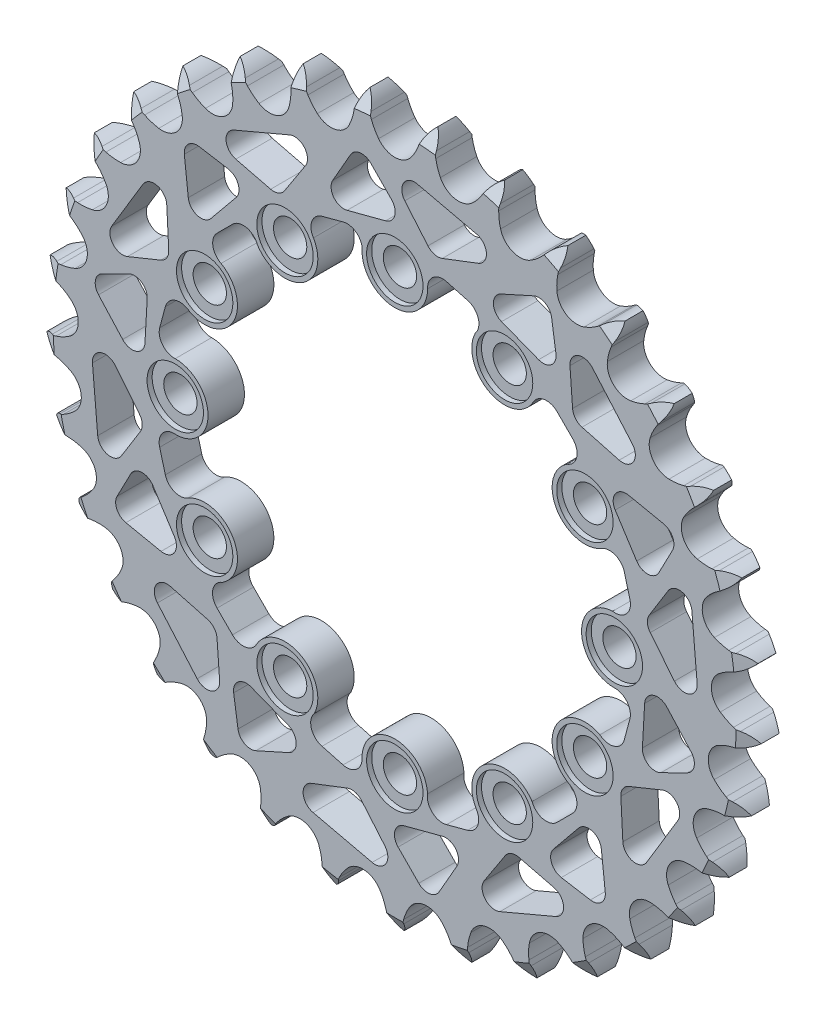
SolidWorks part; units mm, degrees
material "7075-T6 (SN)"
ref_plane "Front Plane" through (0, 0, 0) normal (0, 0, 1) x (1, 0, 0)
ref_plane "Top Plane" through (0, 0, 0) normal (0, 1, 0) x (1, 0, 0)
ref_plane "Right Plane" through (0, 0, 0) normal (1, 0, 0) x (0, 0, -1)
sketch "Work Sketch" plane through (0, 0, 0) normal (0, 0, 1) x (1, 0, 0)
  line L0 (0, 0) -> (0, 160.4542) construction
  line L1 (-112.0919, 66.8027) -> (87.2579, 66.8027) construction
  line L2 (5.0834, 120.8822) -> (5.0834, 112.9699) construction
  line L3 (-12.8497, 70.6081) -> (16.7256, 70.6081) construction
  line L4 (5.0834, 70.6081) -> (-6.0658, 62.2619) construction
  line L5 (5.0834, 70.6081) -> (-4.6352, 66.9715) construction
  line L6 (-4.6352, 66.9715) -> (-6.998, 73.2861)
  line L7 (-11.5114, 65.7464) -> (-7.1525, 65.7464) construction
  line L8 (-11.0622, 124.7602) -> (-11.0622, 110.2345) construction
  line L9 (0, 0) -> (-4.0639, 42.5596) construction
  circle A0 centre (0, 0) radius 66.8027
  circle A1 centre (0, 66.8027) radius 4.0088
  arc A2 (-4.6352, 66.9715) -> (-3.2092, 64.4003) centre (5.0609, 70.6677) ccw
  circle A3 centre (-11.0622, 65.7464) radius 6.4488
  point P23 (-3.2092, 64.4003)
  dimension "D1" = 133.6054
  dimension "D8" = 10.3767
  dimension "D2" = 8.0177
  dimension "D3" = 5.0834
  dimension "D4" = 3.8054
  dimension "D5" = 36.818
  dimension "D6" = 16.303
  dimension "D7" = 10.3767
  dimension "D9" = 1.0563
  dimension "D10" = 11.0622
  dimension "D11" = 5.455
sketch "Teeth Sketch" plane through (0, 0, 0) normal (0, 0, 1) x (1, 0, 0)
  line L0 (5.0224, 68.0064) -> (4.6352, 66.9715)
  line L1 (-8.8439, 92.6176) -> (-5.6513, 59.1829) construction
  line L2 (0, 0) -> (-12.8498, 132.1321) construction
  line L3 (7.9387, 67.7279) -> (8.123, 66.6385)
  line L4 (19011.2087, -199094.3845) -> (-19015.2726, 199136.9441) construction
  line L5 (0, 146.3285) -> (0, 56.9858) construction
  line L6 (17.8019, 65.8269) -> (17.2258, 64.8841)
  line L7 (0, -200000) -> (0, 200160.4542) construction
  line L8 (20.6128, 65.0016) -> (20.5877, 63.897)
  line L9 (-4.6352, 66.9715) -> (-6.998, 73.2861) construction
  line L10 (43.2949, 52.6844) -> (42.861, 51.6682)
  line L11 (-5.0224, 68.0064) -> (-4.6352, 66.9715)
  line L12 (29.938, 61.2683) -> (29.1939, 60.4515)
  line L13 (32.5419, 59.9259) -> (32.3082, 58.846)
  line L14 (40.9921, 54.4953) -> (40.1069, 53.8341)
  line L15 (50.5647, 45.7527) -> (49.5703, 45.271)
  line L16 (52.4831, 43.5387) -> (51.8648, 42.623)
  line L17 (58.3096, 35.3565) -> (57.2421, 35.0716)
  line L18 (59.7744, 32.8194) -> (58.9939, 32.0373)
  line L19 (63.9472, 23.6824) -> (62.845, 23.6047)
  line L20 (64.9053, 20.9139) -> (63.9909, 20.2936)
  line L21 (67.2735, 11.1523) -> (66.1765, 11.2846)
  line L22 (67.6904, 8.2526) -> (66.6751, 7.8165)
  line L23 (68.1683, -1.7808) -> (67.1162, -1.4433)
  line L24 (68.0289, -4.7071) -> (66.9495, -4.9431)
  line L25 (66.5994, -14.6496) -> (65.6302, -14.119)
  line L26 (65.9088, -17.4966) -> (64.8042, -17.524)
  line L27 (62.6234, -26.9889) -> (61.7722, -26.2845)
  line L28 (61.4065, -29.6537) -> (60.3166, -29.4716)
  line L29 (56.3841, -38.3527) -> (55.6815, -37.4999)
  line L30 (54.6848, -40.739) -> (53.6491, -40.354)
  line L31 (48.1068, -48.3304) -> (47.5783, -47.3601)
  line L32 (45.9866, -50.352) -> (45.0425, -49.7779)
  line L33 (38.0909, -56.5613) -> (37.7556, -55.5085)
  line L34 (35.6264, -58.1451) -> (34.808, -57.4027)
  line L35 (26.6983, -62.7479) -> (26.5682, -61.6506)
  line L36 (23.9786, -63.8367) -> (23.3155, -62.9529)
  line L37 (14.3407, -66.6666) -> (14.4207, -65.5646)
  line L38 (11.4641, -67.221) -> (10.9802, -66.2277)
  line L39 (1.4648, -68.1759) -> (1.7519, -67.1089)
  line L40 (-1.4648, -68.1759) -> (-1.7519, -67.1089)
  line L41 (-11.4641, -67.221) -> (-10.9802, -66.2277)
  line L42 (-14.3407, -66.6666) -> (-14.4207, -65.5646)
  line L43 (-23.9786, -63.8367) -> (-23.3155, -62.9529)
  line L44 (-26.6983, -62.7479) -> (-26.5682, -61.6506)
  line L45 (-35.6264, -58.1451) -> (-34.808, -57.4027)
  line L46 (-38.0909, -56.5613) -> (-37.7556, -55.5085)
  line L47 (-45.9866, -50.352) -> (-45.0425, -49.7779)
  line L48 (-48.1068, -48.3304) -> (-47.5783, -47.3601)
  line L49 (-54.6848, -40.739) -> (-53.6491, -40.354)
  line L50 (-56.3841, -38.3527) -> (-55.6815, -37.4999)
  line L51 (-61.4065, -29.6537) -> (-60.3166, -29.4716)
  line L52 (-62.6234, -26.9889) -> (-61.7722, -26.2845)
  line L53 (-65.9088, -17.4966) -> (-64.8042, -17.524)
  line L54 (-66.5994, -14.6496) -> (-65.6302, -14.119)
  line L55 (-68.0289, -4.7071) -> (-66.9495, -4.9431)
  line L56 (-68.1683, -1.7808) -> (-67.1162, -1.4433)
  line L57 (-67.6904, 8.2526) -> (-66.6751, 7.8165)
  line L58 (-67.2735, 11.1523) -> (-66.1765, 11.2846)
  line L59 (-64.9053, 20.9139) -> (-63.9909, 20.2936)
  line L60 (-63.9472, 23.6824) -> (-62.845, 23.6047)
  line L61 (-59.7744, 32.8194) -> (-58.9939, 32.0373)
  line L62 (-58.3096, 35.3565) -> (-57.2421, 35.0716)
  line L63 (-52.4831, 43.5387) -> (-51.8648, 42.623)
  line L64 (-50.5647, 45.7527) -> (-49.5703, 45.271)
  line L65 (-43.2949, 52.6844) -> (-42.861, 51.6682)
  line L66 (-40.9921, 54.4953) -> (-40.1069, 53.8341)
  line L67 (-32.5419, 59.9259) -> (-32.3082, 58.846)
  line L68 (-29.938, 61.2683) -> (-29.1939, 60.4515)
  line L69 (-20.6128, 65.0016) -> (-20.5877, 63.897)
  line L70 (-17.8019, 65.8269) -> (-17.2258, 64.8841)
  line L71 (-7.9387, 67.7279) -> (-8.123, 66.6385)
  arc A0 (-6.7346, 70.5274) -> (-5.0224, 68.0064) centre (-11.0622, 65.7464) cw
  circle A1 centre (-11.0622, 65.7464) radius 6.4488 construction
  arc A2 (-3.2092, 64.4003) -> (-4.6352, 66.9715) centre (5.0609, 70.6677) cw
  arc A3 (-4.6352, 66.9715) -> (-3.2092, 64.4003) centre (5.0609, 70.6677) ccw construction
  circle A4 centre (0, 66.8027) radius 4.0088 construction
  arc A5 (-3.2092, 64.4003) -> (3.2092, 64.4003) centre (0, 66.8027) ccw
  arc A6 (3.2092, 64.4003) -> (4.6352, 66.9715) centre (-5.0609, 70.6677) ccw
  arc A7 (6.7346, 70.5274) -> (5.0224, 68.0064) centre (11.0622, 65.7464) ccw
  arc A8 (6.7346, 70.5274) -> (7.9387, 67.7279) centre (1.5803, 66.6518) cw
  arc A9 (9.0366, 63.8438) -> (8.123, 66.6385) centre (18.3434, 68.4328) cw
  arc A10 (9.0366, 63.8438) -> (15.3391, 62.6291) centre (12.6425, 65.5955) ccw
  arc A11 (15.3391, 62.6291) -> (17.2258, 64.8841) centre (8.4044, 70.3484) ccw
  arc A12 (19.9603, 67.9784) -> (17.8019, 65.8269) centre (23.3049, 62.4647) ccw
  arc A13 (19.9603, 67.9784) -> (20.6128, 65.0016) centre (14.1657, 65.1482) cw
  arc A14 (20.9558, 60.9799) -> (20.5877, 63.897) centre (30.9629, 63.7246) cw
  arc A15 (20.9558, 60.9799) -> (26.9145, 58.5944) centre (24.8281, 62.0175) ccw
  arc A16 (26.9145, 58.5944) -> (29.1939, 60.4515) centre (21.5661, 67.4865) ccw
  arc A17 (32.4645, 62.9724) -> (29.938, 61.2683) centre (34.7052, 56.9254) ccw
  arc A18 (32.4645, 62.9724) -> (32.5419, 59.9259) centre (26.2391, 61.29) cw
  arc A19 (32.1176, 55.912) -> (32.3082, 58.846) centre (42.4634, 56.7133) cw
  arc A20 (32.1176, 55.912) -> (37.5172, 52.4419) centre (36.1163, 56.198) ccw
  arc A21 (37.5172, 52.4419) -> (40.1069, 53.8341) centre (33.9483, 62.1856) ccw
  arc A22 (43.7955, 55.6905) -> (40.9921, 54.4953) centre (44.8513, 49.3287) ccw
  arc A23 (43.7955, 55.6905) -> (43.2949, 52.6844) centre (37.3641, 55.2167) cw
  arc A24 (42.1187, 48.8233) -> (42.861, 51.6682) centre (52.429, 47.6521) cw
  arc A25 (42.1187, 48.8233) -> (46.7639, 44.3941) centre (46.0991, 48.3474) ccw
  arc A26 (46.7639, 44.3941) -> (49.5703, 45.271) centre (45.1035, 54.637) ccw
  arc A27 (53.5435, 46.3957) -> (50.5647, 45.7527) centre (53.3763, 39.9491) ccw
  arc A28 (53.5435, 46.3957) -> (52.4831, 43.5387) centre (47.1387, 47.1476) cw
  arc A29 (50.5974, 39.97) -> (51.8648, 42.623) centre (60.4998, 36.8687) cw
  arc A30 (50.5974, 39.97) -> (54.3205, 34.7417) centre (54.4159, 38.7494) ccw
  arc A31 (54.3205, 34.7417) -> (57.2421, 35.0716) centre (54.6285, 45.1138) ccw
  arc A32 (61.3564, 35.4241) -> (58.3096, 35.3565) centre (59.9721, 29.1257) ccw
  arc A33 (61.3564, 35.4241) -> (59.7744, 32.8194) centre (55.2096, 37.3746) cw
  arc A34 (57.2474, 29.6721) -> (58.9939, 32.0373) centre (66.384, 24.7528) cw
  arc A35 (57.2474, 29.6721) -> (59.9137, 23.8336) centre (60.7659, 27.7508) ccw
  arc A36 (59.9137, 23.8336) -> (62.845, 23.6047) centre (62.1792, 33.96) ccw
  arc A37 (66.9516, 23.1722) -> (63.9472, 23.6824) centre (64.4004, 17.2495) ccw
  arc A38 (66.9516, 23.1722) -> (64.9053, 20.9139) centre (61.2851, 26.2507) cw
  arc A39 (61.8283, 18.3017) -> (63.9909, 20.2936) centre (69.8688, 11.7422) cw
  arc A40 (61.8283, 18.3017) -> (63.3416, 12.0642) centre (64.9196, 15.7493) ccw
  arc A41 (63.3416, 12.0642) -> (66.1765, 11.2846) centre (67.4825, 21.5788) ccw
  arc A42 (70.1271, 10.0828) -> (67.2735, 11.1523) centre (66.5011, 4.7499) ccw
  arc A43 (70.1271, 10.0828) -> (67.6904, 8.2526) centre (65.1456, 14.178) cw
  arc A44 (64.1746, 6.2699) -> (66.6751, 7.8165) centre (70.8284, -1.6927) cw
  arc A45 (64.1746, 6.2699) -> (64.48, -0.1413) centre (66.727, 3.1786) ccw
  arc A46 (64.48, -0.1413) -> (67.1162, -1.4433) centre (70.3468, 8.4177) ccw
  arc A47 (70.768, -3.3711) -> (68.1683, -1.7808) centre (66.1983, -7.9213) ccw
  arc A48 (70.768, -3.3711) -> (68.0289, -4.7071) centre (66.6515, 1.5929) cw
  arc A49 (64.2015, -5.9885) -> (66.9495, -4.9431) centre (69.2281, -15.0665) cw
  arc A50 (64.2015, -5.9885) -> (63.2881, -12.3417) centre (66.1227, -9.507) ccw
  arc A51 (63.2881, -12.3417) -> (65.6302, -14.119) centre (70.6686, -5.0476) ccw
  arc A52 (68.8511, -16.7031) -> (66.5994, -14.6496) centre (63.5029, -20.3063) ccw
  arc A53 (68.8511, -16.7031) -> (65.9088, -17.4966) centre (65.7485, -11.0498) cw
  arc A54 (61.908, -18.0305) -> (64.8042, -17.524) centre (65.1257, -27.8957) cw
  arc A55 (61.908, -18.0305) -> (59.8087, -24.096) centre (63.1286, -21.849) ccw
  arc A56 (59.8087, -24.096) -> (61.7722, -26.2845) centre (68.4363, -18.3305) ccw
  arc A57 (64.4458, -29.4314) -> (62.6234, -26.9889) centre (58.5123, -31.9573) ccw
  arc A58 (64.4458, -29.4314) -> (61.4065, -29.6537) centre (62.4691, -23.2931) cw
  arc A59 (57.3769, -29.4209) -> (60.3166, -29.4716) centre (58.6695, -39.7167) cw
  arc A60 (57.3769, -29.4209) -> (54.1677, -34.9794) centre (57.8528, -33.4013) ccw
  arc A61 (54.1677, -34.9794) -> (55.6815, -37.4999) centre (63.7305, -30.9509) ccw
  arc A62 (57.7113, -41.096) -> (56.3841, -38.3527) centre (51.4069, -42.4533) ccw
  arc A63 (57.7113, -41.096) -> (54.6848, -40.739) centre (56.932, -34.6945) cw
  arc A64 (50.7721, -39.7478) -> (53.6491, -40.354) centre (50.0928, -50.1023) cw
  arc A65 (50.7721, -39.7478) -> (46.5689, -44.5986) centre (50.4861, -43.7465) ccw
  arc A66 (46.5689, -44.5986) -> (47.5783, -47.3601) centre (56.7213, -42.4527) ccw
  arc A67 (48.8909, -51.2753) -> (48.1068, -48.3304) centre (42.4436, -51.415) ccw
  arc A68 (48.8909, -51.2753) -> (45.9866, -50.352) centre (49.3372, -44.842) cw
  arc A69 (42.3322, -48.6382) -> (45.0425, -49.7779) centre (39.7057, -58.677) cw
  arc A70 (42.3322, -48.6382) -> (37.287, -52.6059) centre (41.2947, -52.5105) ccw
  arc A71 (37.287, -52.6059) -> (37.7556, -55.5085) centre (47.662, -52.4201) ccw
  arc A72 (38.3034, -59.6013) -> (38.0909, -56.5613) centre (31.9463, -58.5183) ccw
  arc A73 (38.3034, -59.6013) -> (35.6264, -58.1451) centre (39.9592, -53.3687) cw
  arc A74 (32.3624, -55.7707) -> (34.808, -57.4027) centre (27.8834, -65.131) cw
  arc A75 (32.3624, -55.7707) -> (26.6574, -58.7118) centre (30.6108, -59.3766) ccw
  arc A76 (26.6574, -58.7118) -> (26.5682, -61.6506) centre (36.8801, -60.4929) ccw
  arc A77 (26.3316, -65.7732) -> (26.6983, -62.7479) centre (20.2943, -63.5067) ccw
  arc A78 (26.3316, -65.7732) -> (23.9786, -63.8367) centre (29.137, -59.9666) cw
  arc A79 (21.2229, -60.8875) -> (23.3155, -62.9529) centre (15.0534, -69.2309) cw
  arc A80 (21.2229, -60.8875) -> (15.0644, -62.6958) centre (18.8205, -64.0967) ccw
  arc A81 (15.0644, -62.6958) -> (14.4207, -65.5646) centre (24.7653, -66.3793) ccw
  arc A82 (13.4081, -69.5679) -> (14.3407, -66.6666) centre (7.9088, -66.1998) ccw
  arc A83 (13.4081, -69.5679) -> (11.4641, -67.221) centre (17.2617, -64.3972) cw
  arc A84 (9.3163, -63.8036) -> (10.9802, -66.2277) centre (1.6794, -70.8287) cw
  arc A85 (9.3163, -63.8036) -> (2.9269, -64.4137) centre (6.35, -66.5002) ccw
  arc A86 (2.9269, -64.4137) -> (1.7519, -67.1089) centre (11.7554, -69.8666) ccw
  arc A87 (0, -70.8482) -> (1.4648, -68.1759) centre (-4.7625, -66.5002) ccw
  arc A88 (0, -70.8482) -> (-1.4648, -68.1759) centre (4.7625, -66.5002) cw
  arc A89 (-2.9269, -64.4137) -> (-1.7519, -67.1089) centre (-11.7554, -69.8666) cw
  arc A90 (-2.9269, -64.4137) -> (-9.3163, -63.8036) centre (-6.35, -66.5002) ccw
  arc A91 (-9.3163, -63.8036) -> (-10.9802, -66.2277) centre (-1.6794, -70.8287) ccw
  arc A92 (-13.4081, -69.5679) -> (-11.4641, -67.221) centre (-17.2617, -64.3972) ccw
  arc A93 (-13.4081, -69.5679) -> (-14.3407, -66.6666) centre (-7.9088, -66.1998) cw
  arc A94 (-15.0644, -62.6958) -> (-14.4207, -65.5646) centre (-24.7653, -66.3793) cw
  arc A95 (-15.0644, -62.6958) -> (-21.2229, -60.8875) centre (-18.8205, -64.0967) ccw
  arc A96 (-21.2229, -60.8875) -> (-23.3155, -62.9529) centre (-15.0534, -69.2309) ccw
  arc A97 (-26.3316, -65.7732) -> (-23.9786, -63.8367) centre (-29.137, -59.9666) ccw
  arc A98 (-26.3316, -65.7732) -> (-26.6983, -62.7479) centre (-20.2943, -63.5067) cw
  arc A99 (-26.6574, -58.7118) -> (-26.5682, -61.6506) centre (-36.8801, -60.4929) cw
  arc A100 (-26.6574, -58.7118) -> (-32.3624, -55.7707) centre (-30.6108, -59.3766) ccw
  arc A101 (-32.3624, -55.7707) -> (-34.808, -57.4027) centre (-27.8834, -65.131) ccw
  arc A102 (-38.3034, -59.6013) -> (-35.6264, -58.1451) centre (-39.9592, -53.3687) ccw
  arc A103 (-38.3034, -59.6013) -> (-38.0909, -56.5613) centre (-31.9463, -58.5183) cw
  arc A104 (-37.287, -52.6059) -> (-37.7556, -55.5085) centre (-47.662, -52.4201) cw
  arc A105 (-37.287, -52.6059) -> (-42.3322, -48.6382) centre (-41.2947, -52.5105) ccw
  arc A106 (-42.3322, -48.6382) -> (-45.0425, -49.7779) centre (-39.7057, -58.677) ccw
  arc A107 (-48.8909, -51.2753) -> (-45.9866, -50.352) centre (-49.3372, -44.842) ccw
  arc A108 (-48.8909, -51.2753) -> (-48.1068, -48.3304) centre (-42.4436, -51.415) cw
  arc A109 (-46.5689, -44.5986) -> (-47.5783, -47.3601) centre (-56.7213, -42.4527) cw
  arc A110 (-46.5689, -44.5986) -> (-50.7721, -39.7478) centre (-50.4861, -43.7465) ccw
  arc A111 (-50.7721, -39.7478) -> (-53.6491, -40.354) centre (-50.0928, -50.1023) ccw
  arc A112 (-57.7113, -41.096) -> (-54.6848, -40.739) centre (-56.932, -34.6945) ccw
  arc A113 (-57.7113, -41.096) -> (-56.3841, -38.3527) centre (-51.4069, -42.4533) cw
  arc A114 (-54.1677, -34.9794) -> (-55.6815, -37.4999) centre (-63.7305, -30.9509) cw
  arc A115 (-54.1677, -34.9794) -> (-57.3769, -29.4209) centre (-57.8528, -33.4013) ccw
  arc A116 (-57.3769, -29.4209) -> (-60.3166, -29.4716) centre (-58.6695, -39.7167) ccw
  arc A117 (-64.4458, -29.4314) -> (-61.4065, -29.6537) centre (-62.4691, -23.2931) ccw
  arc A118 (-64.4458, -29.4314) -> (-62.6234, -26.9889) centre (-58.5123, -31.9573) cw
  arc A119 (-59.8087, -24.096) -> (-61.7722, -26.2845) centre (-68.4363, -18.3305) cw
  arc A120 (-59.8087, -24.096) -> (-61.908, -18.0305) centre (-63.1286, -21.849) ccw
  arc A121 (-61.908, -18.0305) -> (-64.8042, -17.524) centre (-65.1257, -27.8957) ccw
  arc A122 (-68.8511, -16.7031) -> (-65.9088, -17.4966) centre (-65.7485, -11.0498) ccw
  arc A123 (-68.8511, -16.7031) -> (-66.5994, -14.6496) centre (-63.5029, -20.3063) cw
  arc A124 (-63.2881, -12.3417) -> (-65.6302, -14.119) centre (-70.6686, -5.0476) cw
  arc A125 (-63.2881, -12.3417) -> (-64.2015, -5.9885) centre (-66.1227, -9.507) ccw
  arc A126 (-64.2015, -5.9885) -> (-66.9495, -4.9431) centre (-69.2281, -15.0665) ccw
  arc A127 (-70.768, -3.3711) -> (-68.0289, -4.7071) centre (-66.6515, 1.5929) ccw
  arc A128 (-70.768, -3.3711) -> (-68.1683, -1.7808) centre (-66.1983, -7.9213) cw
  arc A129 (-64.48, -0.1413) -> (-67.1162, -1.4433) centre (-70.3468, 8.4177) cw
  arc A130 (-64.48, -0.1413) -> (-64.1746, 6.2699) centre (-66.727, 3.1786) ccw
  arc A131 (-64.1746, 6.2699) -> (-66.6751, 7.8165) centre (-70.8284, -1.6927) ccw
  arc A132 (-70.1271, 10.0828) -> (-67.6904, 8.2526) centre (-65.1456, 14.178) ccw
  arc A133 (-70.1271, 10.0828) -> (-67.2735, 11.1523) centre (-66.5011, 4.7499) cw
  arc A134 (-63.3416, 12.0642) -> (-66.1765, 11.2846) centre (-67.4825, 21.5788) cw
  arc A135 (-63.3416, 12.0642) -> (-61.8283, 18.3017) centre (-64.9196, 15.7493) ccw
  arc A136 (-61.8283, 18.3017) -> (-63.9909, 20.2936) centre (-69.8688, 11.7422) ccw
  arc A137 (-66.9516, 23.1722) -> (-64.9053, 20.9139) centre (-61.2851, 26.2507) ccw
  arc A138 (-66.9516, 23.1722) -> (-63.9472, 23.6824) centre (-64.4004, 17.2495) cw
  arc A139 (-59.9137, 23.8336) -> (-62.845, 23.6047) centre (-62.1792, 33.96) cw
  arc A140 (-59.9137, 23.8336) -> (-57.2474, 29.6721) centre (-60.7659, 27.7508) ccw
  arc A141 (-57.2474, 29.6721) -> (-58.9939, 32.0373) centre (-66.384, 24.7528) ccw
  arc A142 (-61.3564, 35.4241) -> (-59.7744, 32.8194) centre (-55.2096, 37.3746) ccw
  arc A143 (-61.3564, 35.4241) -> (-58.3096, 35.3565) centre (-59.9721, 29.1257) cw
  arc A144 (-54.3205, 34.7417) -> (-57.2421, 35.0716) centre (-54.6285, 45.1138) cw
  arc A145 (-54.3205, 34.7417) -> (-50.5974, 39.97) centre (-54.4159, 38.7494) ccw
  arc A146 (-50.5974, 39.97) -> (-51.8648, 42.623) centre (-60.4998, 36.8687) ccw
  arc A147 (-53.5435, 46.3957) -> (-52.4831, 43.5387) centre (-47.1387, 47.1476) ccw
  arc A148 (-53.5435, 46.3957) -> (-50.5647, 45.7527) centre (-53.3763, 39.9491) cw
  arc A149 (-46.7639, 44.3941) -> (-49.5703, 45.271) centre (-45.1035, 54.637) cw
  arc A150 (-46.7639, 44.3941) -> (-42.1187, 48.8233) centre (-46.0991, 48.3474) ccw
  arc A151 (-42.1187, 48.8233) -> (-42.861, 51.6682) centre (-52.429, 47.6521) ccw
  arc A152 (-43.7955, 55.6905) -> (-43.2949, 52.6844) centre (-37.3641, 55.2167) ccw
  arc A153 (-43.7955, 55.6905) -> (-40.9921, 54.4953) centre (-44.8513, 49.3287) cw
  arc A154 (-37.5172, 52.4419) -> (-40.1069, 53.8341) centre (-33.9483, 62.1856) cw
  arc A155 (-37.5172, 52.4419) -> (-32.1176, 55.912) centre (-36.1163, 56.198) ccw
  arc A156 (-32.1176, 55.912) -> (-32.3082, 58.846) centre (-42.4634, 56.7133) ccw
  arc A157 (-32.4645, 62.9724) -> (-32.5419, 59.9259) centre (-26.2391, 61.29) ccw
  arc A158 (-32.4645, 62.9724) -> (-29.938, 61.2683) centre (-34.7052, 56.9254) cw
  arc A159 (-26.9145, 58.5944) -> (-29.1939, 60.4515) centre (-21.5661, 67.4865) cw
  arc A160 (-26.9145, 58.5944) -> (-20.9558, 60.9799) centre (-24.8281, 62.0175) ccw
  arc A161 (-20.9558, 60.9799) -> (-20.5877, 63.897) centre (-30.9629, 63.7246) ccw
  arc A162 (-19.9603, 67.9784) -> (-20.6128, 65.0016) centre (-14.1657, 65.1482) ccw
  arc A163 (-19.9603, 67.9784) -> (-17.8019, 65.8269) centre (-23.3049, 62.4647) cw
  arc A164 (-15.3391, 62.6291) -> (-17.2258, 64.8841) centre (-8.4044, 70.3484) cw
  arc A165 (-15.3391, 62.6291) -> (-9.0366, 63.8438) centre (-12.6425, 65.5955) ccw
  arc A166 (-9.0366, 63.8438) -> (-8.123, 66.6385) centre (-18.3434, 68.4328) ccw
  arc A167 (-6.7346, 70.5274) -> (-7.9387, 67.7279) centre (-1.5803, 66.6518) ccw
  point P77 (0, 0)
  dimension "D1" = 5.455
  dimension "D2" = 5.555
  dimension "D3" = 33
extrude "Extrusion" add sketch "Teeth Sketch" along normal blind 7.2136 contours A0 region at (0, 0, 0)
ref_axis "Axis2" through (0, 0, 38.9715) along (0, 0, -1)
hole_wizard "M6 Clearance Hole1" positions "Sketch6" profile "Sketch7" hole size "M6" standard "ANSI Metric"
sketch "Sketch6" plane through (0, 0, 0) normal (0, 0, -1) x (-1, 0, 0)
  circle A0 centre (0, 0) radius 43.5
  point P0 (0, 43.5)
  dimension "D1" = 87
sketch "Sketch7" plane through (0, 43.5, 0) normal (1, 0, 0) x (0, 1, 0)
  line L0 (0, 0) -> (0, 19.2548)
  line L1 (0, 19.2548) -> (3.3, 17.272)
  line L2 (3.3, 17.272) -> (3.3, 0)
  line L5 (3.3, 0) -> (0, 0)
  line L10 (0, 19.2548) -> (-3.3, 17.272) construction
  line L11 (0, -6.35) -> (0, 107.95) construction
  dimension "Hole Dia." = 6.6
  dimension "Hole Depth" = 17.272
  dimension "Drill Angle" = 118
pattern_circular "CirPattern1" count 12 over 360 about axis through (0, 0, 38.9715) along (0, 0, -1) of "M6 Clearance Hole1"
sketch "Sketch8" plane through (0, 0, 0) normal (0, 0, -1) x (-1, 0, 0)
  circle A0 centre (0, 0) radius 37
  dimension "D1" = 74
extrude "Cut-Extrude1" cut sketch "Sketch8" against normal through all both and the other way through all
ref_plane "Sprocket Center Plane" through (0, 0, 3.6068) normal (0, 0, 1) x (1, 0, 0)
sketch "Pitch Circle" plane through (0, 0, 3.6068) normal (0, 0, -1) x (-1, 0, 0)
  circle A0 centre (0, 0) radius 66.8027 construction
  dimension "D1" = 133.6054
ref_plane "Center Plane" through (0, 0, 3.6068) normal (0, 0, 1) x (1, 0, 0)
ref_axis "Axis1" through (0, 0, 7.2136) along (0, 0, -1)
sketch "Sketch5" plane through (0, 0, 0) normal (1, 0, 0) x (0, 0, -1)
  line L0 (-1.8288, -70.8482) -> (-5.3848, -70.8482)
  line L1 (-7.2136, -51.2753) -> (0, -51.2753) construction
  line L2 (-5.3848, -70.8482) -> (-5.3848, -67.6547)
  line L3 (-5.3848, -67.6547) -> (-7.2136, -67.6547)
  line L4 (-7.2136, -67.6547) -> (-5.3848, -70.8482)
  line L5 (-7.2136, -67.6547) -> (-7.2136, -70.8482)
  line L6 (-7.2136, -70.8482) -> (-5.3848, -70.8482)
  line L8 (-7.2136, -70.8482) -> (0, -70.8482) construction
  dimension "D1" = 3.556
  dimension "D2" = 3.1936
  dimension "D3" = 1.8288
revolve "Cut-Revolve1" cut sketch "Sketch5" angle 360 about axis through (0, 0, 7.2136) along (0, 0, -1) region at (0, -69.7837, 6.604)
mirror "Mirror1" about plane through (0, 0, 3.6068) normal (0, 0, 1) of "Cut-Revolve1"
sketch "Sketch10" plane through (0, 0, 0) normal (0, 0, 1) x (1, 0, 0)
  circle A0 centre (-43.5, 0) radius 5.588
  dimension "D1" = 11.176
extrude "Cut-Extrude2" cut sketch "Sketch10" against normal blind 1.016 from surface starting at face at (-37, 0, 7.2136)
pattern_circular "CirPattern2" count 12 over 360 about axis through (0, 0, 38.9715) along (0, 0, -1) of "Cut-Extrude2"
ref_plane "Half Plane" through (0, 0, 3.6068) normal (0, 0, 1) x (1, 0, 0)
sketch "Motor Shaft Sprocket Dimensions" plane through (0, 0, 3.6068) normal (0, 0, 1) x (1, 0, 0)
  line L0 (0, 0) -> (-177.8, 0)
  line L1 (-177.8, 0) -> (-177.8, 23.6982)
  line L2 (-180.2273, 51.0991) -> (-5.8945, 66.5421)
  line L3 (-187.3193, -2.1104) -> (-23.1174, -62.6753)
  line L4 (-5.8945, 66.5421) -> (0, 0)
  line L5 (0, 0) -> (-23.1174, -62.6753)
  circle A0 centre (-177.8, 23.6982) radius 27.5082
  circle A1 centre (0, 0) radius 66.8027 construction
  dimension "D3" = 55.0164
  dimension "D1" = 177.8
  dimension "D2" = 23.6982
  dimension "D4" = 205.308
sketch "Sketch11" plane through (0, 0, 0) normal (0, 0, 1) x (1, 0, 0)
  line L0 (-167.2094, -55.7997) -> (-36.0913, 46.3337)
  line L1 (-145.9214, -98.8914) -> (14.8674, -56.8186)
  circle A2 centre (-152.1323, -75.1555) radius 24.535
  circle A3 centre (0, 0) radius 58.7316
  dimension "D2" = 117.4631
  dimension "D3" = 49.07
  dimension "D1" = 169.6838
sketch "Sketch12" plane through (0, 0, 7.2136) normal (0, 0, 1) x (1, 0, 0)
  line L0 (0, 43.5) -> (21.75, 37.6721) construction
  line L1 (9.5763, 35.7393) -> (13.8192, 51.5738) construction
  line L2 (10.2476, 46.5861) -> (14.4184, 45.4686) construction
  line L6 (9.4955, 43.681) -> (13.6664, 42.5634) construction
  line L7 (10.2476, 46.5861) -> (14.4184, 45.4686)
  circle A0 centre (21.75, 37.6721) radius 5.588 construction
  circle A1 centre (0, 43.5) radius 5.588 construction
  circle A2 centre (21.75, 37.6721) radius 5.588 construction
  circle A3 centre (0, 43.5) radius 5.588 construction
  circle A4 centre (0, 43.5) radius 6.5 construction
  circle A5 centre (21.75, 37.6721) radius 6.5 construction
  circle A6 centre (0, 0) radius 37 construction
  arc A7 (0, 37) -> (18.5, 32.0429) centre (0, 0) cw
  circle A8 centre (0, 0) radius 37 construction
  arc A9 (10.2476, 46.5861) -> (6.5, 43.5) centre (9.4955, 43.681) ccw
  arc A10 (14.4184, 45.4686) -> (15.9628, 40.6315) centre (13.6664, 42.5634) cw
  arc A20 (0, 37) -> (6.5, 43.5) centre (0, 43.5) ccw
  arc A21 (15.9628, 40.6315) -> (18.5, 32.0429) centre (21.75, 37.6721) ccw
  dimension "D1" = 42.0178
  dimension "D2" = 5.6332
  dimension "D6" = 4.318
  dimension "D7" = 3.0009
extrude "Cut-Extrude3" cut sketch "Sketch12" against normal through all contours A21 A7 A20 A9 L7 A10
pattern_circular "CirPattern3" count 12 over 360 about axis through (0, 0, 7.2136) along (0, 0, -1) of "Cut-Extrude3" reverse direction yes
sketch "Sketch13" plane through (0, 0, 7.2136) normal (0, 0, 1) x (1, 0, 0)
  line L0 (-12.295, 52.6993) -> (-8.767, 58.8746)
  line L1 (-4.7487, 59.3936) -> (-0.6568, 55.2241)
  line L2 (-1.8231, 50.9886) -> (-9.4431, 48.983)
  line L3 (1.9797, 56.3209) -> (6.5673, 50.8863)
  line L4 (9.4175, 50.1531) -> (16.5325, 52.881)
  line L5 (16.1956, 57.7273) -> (4.493, 60.434)
  arc A0 (-4.7487, 59.3936) -> (-8.767, 58.8746) centre (-6.5615, 57.6145) ccw
  arc A1 (-9.4431, 48.983) -> (-12.295, 52.6993) centre (-10.0896, 51.4393) cw
  arc A2 (-1.8231, 50.9886) -> (-0.6568, 55.2241) centre (-2.4696, 53.445) ccw
  arc A3 (9.4175, 50.1531) -> (6.5673, 50.8863) centre (8.5082, 52.5247) cw
  arc A4 (4.493, 60.434) -> (1.9797, 56.3209) centre (3.9206, 57.9593) ccw
  arc A5 (16.5325, 52.881) -> (16.1956, 57.7273) centre (15.6232, 55.2526) ccw
  circle A6 centre (0, 0) radius 43.5 construction
  dimension "D13" = 2.54
  dimension "D15" = 7.62
  dimension "D16" = 2.54
  dimension "D1" = 51.4393
  dimension "D2" = 53.445
  dimension "D3" = 57.6145
  dimension "D4" = 10.0896
  dimension "D5" = 2.4696
  dimension "D6" = 6.5615
  dimension "D7" = 3.9206
  dimension "D8" = 8.5082
  dimension "D9" = 15.6232
  dimension "D10" = 52.5247
  dimension "D11" = 55.2526
  dimension "D12" = 57.9593
  dimension "D14" = 7.112
  dimension "D17" = 7.112
extrude "Cut-Extrude4" cut sketch "Sketch13" against normal through all
pattern_circular "CirPattern5" count 10 over 360 about axis through (0, 0, 38.9715) along (0, 0, -1) of "Cut-Extrude4"
equation "\"P\"= 0.500'//Chain Pitch"
equation "\"N\"= 33'//Number of Teeth"
equation "\"Dr\"= 5 / 16'//Roller Diameter"
equation "\"Ds\"= 1.0005 * \"Dr\" + 0.003'Seating Curve DIameter"
equation "\"R\"= \"Ds\" / 2"
equation "\"A\"= 35 + 60 / \"N\""
equation "\"B\"= 18 - 56 / \"N\""
equation "\"ac\"= 0.8 * \"Dr\""
equation "\"M\"= 0.8 * \"Dr\" * cos ( 35 + 60 / \"N\" )"
equation "\"T\"= 0.8 * \"Dr\" * sin ( 35 + 60 / \"N\" )"
equation "\"E\"= 1.3025 * \"Dr\" + 0.0015"
equation "\"Chordal Length of Arc xy\"= ( 2.605 * \"Dr\" + 0.003 ) * sin ( 9 - 28 / \"N\" )"
equation "\"yz\"= \"Dr\" * ( 1.4 * sin ( 17 - 64 / \"N\" ) - 0.8 * sin ( 18 - 56 / \"N\" ) )"
equation "\"ab\"= 1.4 * \"Dr\""
equation "\"W\"= 1.4 * \"Dr\" * cos ( 180 / \"N\" )"
equation "\"V\"= 1.4 * \"Dr\" * sin ( 180 / \"N\" )"
equation "\"F\"= \"Dr\" * ( 0.8 * cos ( 18 - 56 / \"N\" ) + 1.4 * cos ( 17 - 64 / \"N\" ) - 1.3025 )"
equation "\"H\"= sqr ( \"F\" ^ 2 - ( 1.4 * \"Dr\" - \"P\" / 2 ) ^ 2 )"
equation "\"S\"= \"P\" / 2 * cos ( 180 / \"N\" ) + \"H\" * sin ( 180 / \"N\" )"
equation "\"PD\"= \"P\" / ( sin ( 180 / \"N\" ) )"
equation "\"D1@Work Sketch\" = \"PD\""
equation "\"D3@Work Sketch\" = \"M\""
equation "\"D4@Work Sketch\" = \"T\""
equation "\"D5@Work Sketch\" = \"A\""
equation "\"D6@Work Sketch\" = \"B\""
equation "\"D7@Work Sketch\" = \"E\""
equation "\"D8@Work Sketch\" = \"E\""
equation "\"D9@Work Sketch\" = \"V\""
equation "\"D10@Work Sketch\" = \"W\""
equation "\"D2@Work Sketch\" = \"R\" * 2"
equation "\"D11@Work Sketch\" = 180 / \"N\""
equation "\"D2@Teeth Sketch\" = 180 / \"N\" + 0.1"
equation "\"D3@Teeth Sketch\" = \"N\""
equation "\"Edge Thickness\"=0.5"
equation "\"D1@Pitch Circle\"=\"PD\""
equation "\"ST\"= 0.284'//Sprocket Thickness"
